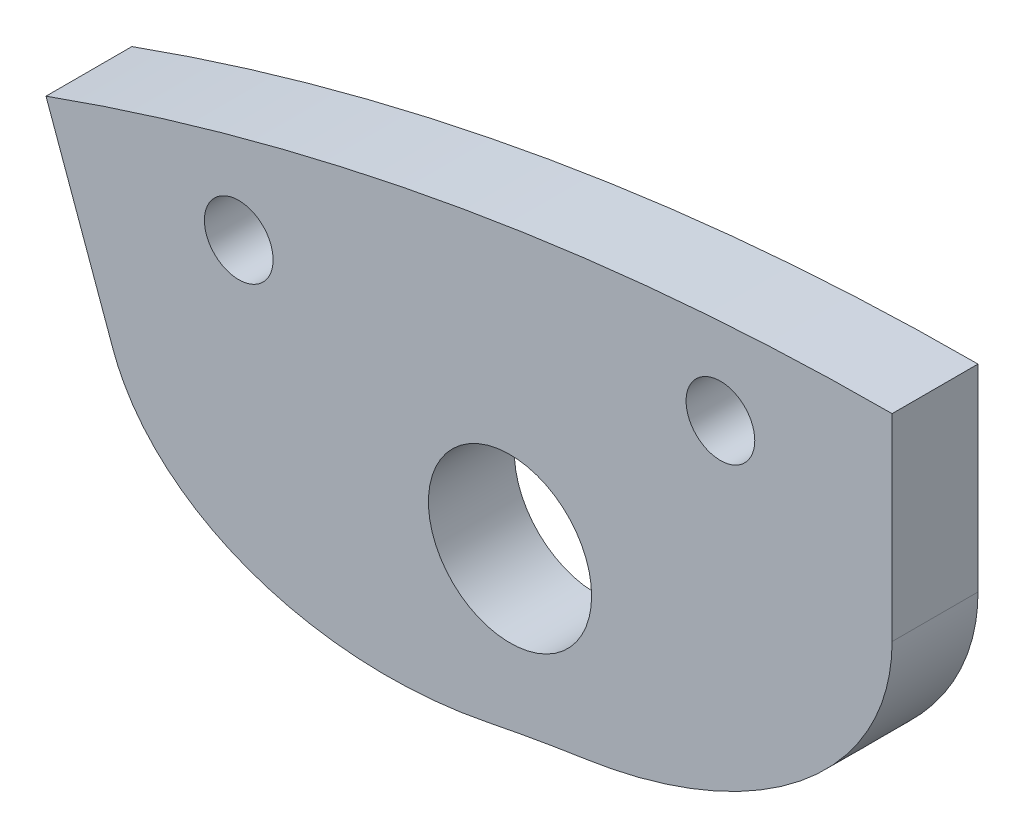
SolidWorks part; units mm, degrees
ref_plane "Piano frontale" through (0, 0, 0) normal (0, 0, 1) x (1, 0, 0)
ref_plane "Piano superiore" through (0, 0, 0) normal (0, 1, 0) x (1, 0, 0)
ref_plane "Piano destro" through (0, 0, 0) normal (1, 0, 0) x (0, 0, -1)
sketch "Schizzo1" plane through (0, 0, 0) normal (0, 0, 1) x (1, 0, 0)
  line L0 (0, 145) -> (0, 120)
  line L1 (-49.2512, 136.3793) -> (-40.7596, 112.8656)
  line L2 (0, 0) -> (0, 145) construction
  line L3 (0, 0) -> (-49.2512, 136.3793) construction
  line L4 (0, 145) -> (-49.2512, 136.3793) construction
  arc A0 (0, 145) -> (-49.2512, 136.3793) centre (0, 0) ccw
  arc A1 (0, 120) -> (-40.7596, 112.8656) centre (0, 0) ccw
  dimension "D2" = 120
  dimension "D3" = 145
  dimension "D1" = 50
extrude "Estrusione-Estrusione1" add sketch "Schizzo1" along normal blind 5
sketch "Schizzo2" plane through (0, 0, 5) normal (0, 0, 1) x (1, 0, 0)
  line L0 (-49.2512, 136.3793) -> (-47.5529, 131.6766) construction
  line L1 (-49.2512, 136.3793) -> (-40.7596, 112.8656) construction
  line L2 (0, 120) -> (0, 145) construction
  arc A0 (-47.5529, 131.6766) -> (0, 140) centre (0, 0) cw construction
  circle A1 centre (-38.0321, 134.7351) radius 2
  circle A2 centre (-9.9936, 139.6429) radius 2
  dimension "D3" = 4
  dimension "D4" = 4
  dimension "D1" = 5
  dimension "D2" = 10
  dimension "D5" = 10
extrude "Taglio-Estrusione1" cut sketch "Schizzo2" against normal blind 5
fillet "Raccordo1" radius 15 1 edges at (-40.7596, 112.8656, 2.5)
fillet "Raccordo2" radius 15 1 edges at (0, 120, 2.5)
sketch "Schizzo3" plane through (0, 0, 5) normal (0, 0, 1) x (1, 0, 0)
  line L0 (-20.6897, 118.203) -> (-22.2414, 127.0682) construction
  line L1 (-23.589, 117.6586) -> (-17.7778, 118.6758) construction
  arc A0 (-17.7778, 118.6758) -> (-23.589, 117.6586) centre (0, 0) ccw construction
  dimension "D1" = 9
  dimension "D3" = 90
sketch "Schizzo4" plane through (0, 0, 5) normal (0, 0, 1) x (1, 0, 0)
  circle A0 centre (-22.2414, 127.0682) radius 4.75
  dimension "D1" = 9.5
extrude "Taglio-Estrusione2" cut sketch "Schizzo4" against normal blind 10
